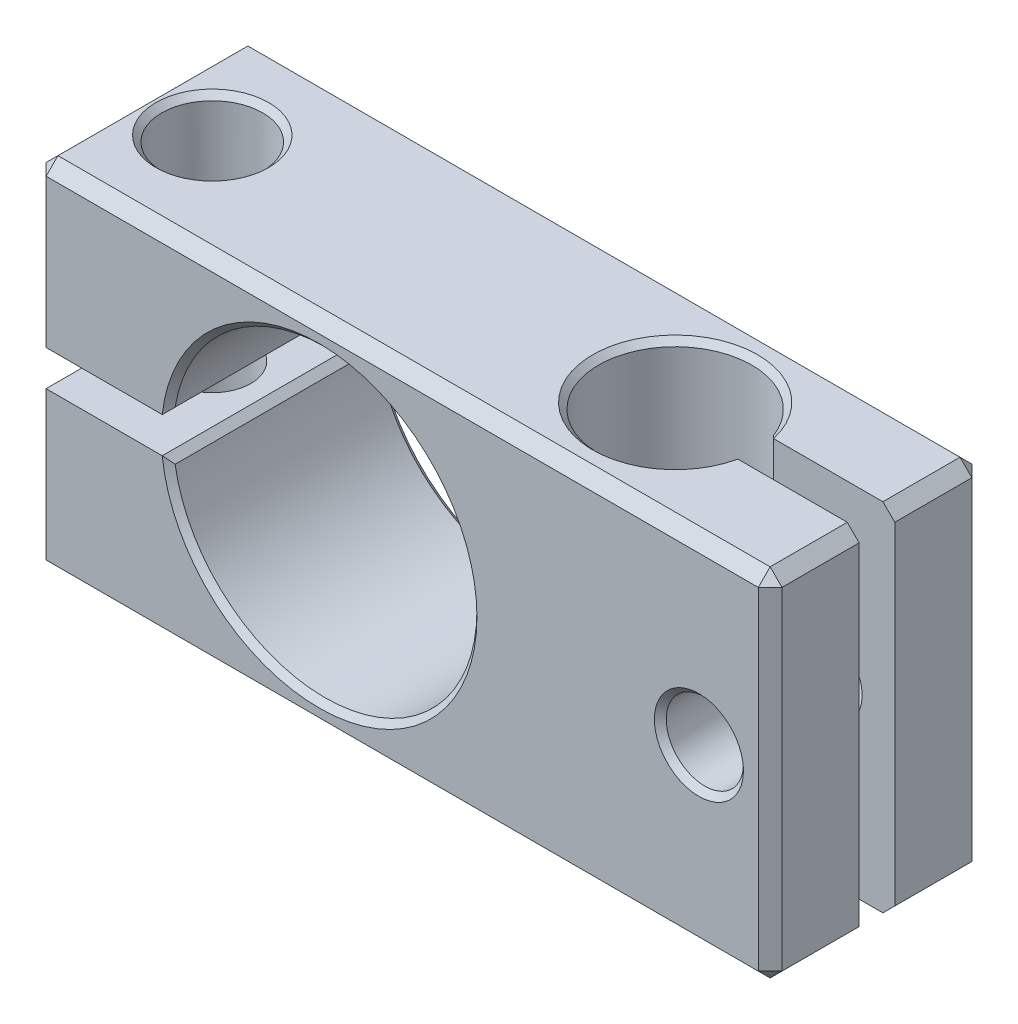
SolidWorks part; units mm, degrees
ref_plane "Plan de face" through (0, 0, 0) normal (0, 0, 1) x (1, 0, 0)
ref_plane "Plan de dessus" through (0, 0, 0) normal (0, 1, 0) x (1, 0, 0)
ref_plane "Plan de droite" through (0, 0, 0) normal (1, 0, 0) x (0, 0, -1)
sketch "Esquisse1" plane through (0, 0, 0) normal (0, 0, 1) x (1, 0, 0)
  line L1 (0, 0) -> (62, 0)
  line L2 (0, 0) -> (0, 30)
  line L3 (0, 30) -> (62, 30)
  line L4 (62, 0) -> (62, 30)
  dimension "D1" = 30
  dimension "D2" = 62
extrude "Boss.-Extru.1" add sketch "Esquisse1" along normal blind 18
sketch "Esquisse2" plane through (0, 0, 18) normal (0, 0, 1) x (1, 0, 0)
  line L0 (0, 15) -> (24, 15) construction
  line L1 (0, 30) -> (0, 0) construction
  circle A0 centre (24, 15) radius 12.8
  dimension "D1" = 25.6
  dimension "D2" = 24
extrude "Enlèv. mat.-Extru.1" cut sketch "Esquisse2" against normal through all both and the other way through all
sketch "Esquisse3" plane through (0, 0, 18) normal (0, 0, 1) x (1, 0, 0)
  line L0 (0, 15) -> (15, 15) construction
  line L1 (0, 30) -> (0, 0) construction
  line L2 (15, 13.5) -> (15, 16.5)
  line L3 (15, 16.5) -> (0, 16.5)
  line L4 (0, 16.5) -> (0, 13.5)
  line L5 (15, 13.5) -> (0, 13.5)
  dimension "D1" = 3
  dimension "D2" = 15
extrude "Enlèv. mat.-Extru.2" cut sketch "Esquisse3" against normal through all both and the other way through all
sketch "Esquisse4" plane through (0, 0, 0) normal (0, -1, 0) x (1, 0, 0)
  line L0 (62, 9) -> (45, 9) construction
  line L1 (62, 18) -> (62, 0) construction
  line L2 (0, 9) -> (6, 9) construction
  line L3 (0, 18) -> (0, 0) construction
  circle A0 centre (45, 9) radius 6.45
  circle A1 centre (6, 9) radius 3.25
  dimension "D1" = 12.9
  dimension "D3" = 6.5
  dimension "D2" = 17
  dimension "D4" = 6
extrude "Enlèv. mat.-Extru.3" cut sketch "Esquisse4" against normal through all both and the other way through all
sketch "Esquisse6" plane through (0, 0, 0) normal (0, -1, 0) x (1, 0, 0)
  line L0 (62, 9) -> (47, 9) construction
  line L1 (62, 18) -> (62, 0) construction
  line L2 (47, 7.5) -> (47, 10.5)
  line L3 (47, 10.5) -> (62, 10.5)
  line L4 (62, 10.5) -> (62, 7.5)
  line L5 (47, 7.5) -> (62, 7.5)
  dimension "D1" = 15
  dimension "D2" = 3
extrude "Enlèv. mat.-Extru.4" cut sketch "Esquisse6" against normal through all both and the other way through all
sketch "Esquisse8" plane through (0, 0, 18) normal (0, 0, 1) x (1, 0, 0)
  line L0 (62, 15) -> (56, 15) construction
  line L1 (62, 0) -> (62, 30) construction
  circle A0 centre (56, 15) radius 3.25
  dimension "D1" = 6.5
  dimension "D2" = 6
extrude "Enlèv. mat.-Extru.5" cut sketch "Esquisse8" against normal through all both and the other way through all
sketch "Esquisse9" plane through (0, 30, 0) normal (0, 1, 0) x (1, 0, 0)
  circle A1 centre (6, -9) radius 4.25
  dimension "D1" = 8.5
extrude "Enlèv. mat.-Extru.6" cut sketch "Esquisse9" against normal blind 12.7
sketch "Esquisse10" plane through (0, 0, 0) normal (0, 0, -1) x (-1, 0, 0)
  circle A0 centre (-56, 15) radius 4.25
  dimension "D1" = 8.5
extrude "Enlèv. mat.-Extru.7" cut sketch "Esquisse10" against normal blind 6
chamfer "Chanfrein1" distance 0.5 angle 45 12 edges at (36.8, 15, 0) (38.55, 0, 9) (6, 0, 12.25) (6, 30, 13.25) (51.75, 15, 0) (52.75, 15, 18) (36.8, 15, 18) (38.55, 30, 9) (11.2882, 13.5, 9) (11.2882, 16.5, 9) (51.2732, 15, 7.5) (51.2732, 15, 10.5)
chamfer "Chanfrein2" distance 1 angle 45 18 edges at (0, 23.25, 18) (31, 30, 18) (62, 15, 18) (31, 0, 18) (0, 6.75, 18) (0, 6.75, 0) (0, 23.25, 0) (31, 0, 0) (62, 15, 0) (31, 30, 0) (62, 0, 14.25) (0, 30, 9) (0, 16.5, 9) (0, 13.5, 9) (62, 30, 14.25) (0, 0, 9) (62, 0, 3.75) (62, 30, 3.75)
